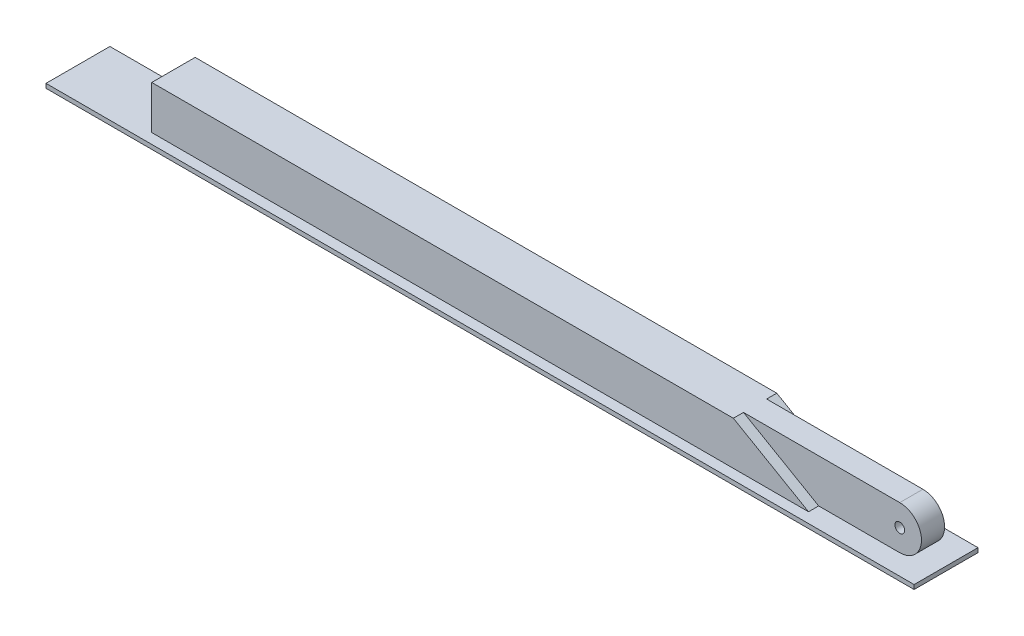
SolidWorks part; units mm, degrees
ref_plane "Front Plane" through (0, 0, 0) normal (0, 0, 1) x (1, 0, 0)
ref_plane "Top Plane" through (0, 0, 0) normal (0, 1, 0) x (1, 0, 0)
ref_plane "Right Plane" through (0, 0, 0) normal (1, 0, 0) x (0, 0, -1)
sketch "Sketch1" plane through (0, 0, 0) normal (0, 0, 1) x (1, 0, 0)
  line L0 (-225, 0) -> (225, 0) construction
  line L1 (-225, 15) -> (225, 15)
  line L2 (-225, -15) -> (225, -15)
  arc A0 (-225, 15) -> (-225, -15) centre (-225, 0) ccw
  arc A1 (225, -15) -> (225, 15) centre (225, 0) ccw
  point P2 (0, 0)
  dimension "D1" = 450
  dimension "D2" = 30
extrude "Boss-Extrude1" add sketch "Sketch1" along normal mid plane 30
hole_wizard "H (0.266) Diameter Hole1" positions "Sketch2" profile "Sketch4" hole size "H" standard "ANSI Inch" end condition through all
sketch "Sketch2" plane through (0, 0, 15) normal (0, 0, 1) x (1, 0, 0)
  point P0 (-225, 0)
  point P3 (225, 0)
sketch "Sketch4" plane through (-225, 0, 15) normal (1, 0, 0) x (0, -1, 0)
  line L0 (0, 0) -> (0, 30)
  line L1 (0, 30) -> (3.3782, 30)
  line L2 (3.3782, 30) -> (3.3782, 0)
  line L5 (3.3782, 0) -> (0, 0)
  line L11 (0, -6.35) -> (0, 107.95) construction
  dimension "Thru Hole Dia." = 6.7564
  dimension "Thru Hole Depth" = 30
sketch "Sketch5" plane through (0, 15, 0) normal (0, 1, 0) x (1, 0, 0)
  line L1 (-257, 8) -> (-217, 8)
  line L2 (-257, 8) -> (-257, -8)
  line L3 (-257, -8) -> (-217, -8)
  line L4 (-217, 8) -> (-217, -8)
  line L5 (-217, 0) -> (0, 0) construction
  line L6 (-225, -15) -> (-225, 15) construction
  line L7 (225, -15) -> (225, 15) construction
  line L8 (217, 28.9161) -> (257, 28.9161)
  line L9 (217, 28.9161) -> (217, 8)
  line L10 (217, 8) -> (257, 8)
  line L11 (257, 28.9161) -> (257, 8)
  line L12 (217, -28.9161) -> (257, -28.9161)
  line L13 (217, -28.9161) -> (217, -8)
  line L14 (217, -8) -> (257, -8)
  line L15 (257, -28.9161) -> (257, -8)
  dimension "D1" = 16
  dimension "D2" = 8
  dimension "D3" = 40
  dimension "D4" = 8
extrude "Cut-Extrude1" cut sketch "Sketch5" against normal through all
sketch "Sketch6" plane through (0, 15, 0) normal (0, 1, 0) x (1, 0, 0)
  line L0 (217, 15) -> (217, 8) construction
  line L1 (-262.0368, 59.0418) -> (167, 59.0418)
  line L2 (-262.0368, 59.0418) -> (-262.0368, -68.39)
  line L3 (-262.0368, -68.39) -> (167, -68.39)
  line L4 (167, 59.0418) -> (167, -68.39)
  dimension "D1" = 50
extrude "Cut-Extrude2" cut sketch "Sketch6" against normal through all
sketch "Sketch10" plane through (167, 0, 0) normal (-1, 0, 0) x (0, 0, 1)
  line L1 (15, -15) -> (-15, -15)
  line L2 (15, -15) -> (15, 15)
  line L3 (15, 15) -> (-15, 15)
  line L4 (-15, -15) -> (-15, 15)
  line L5 (15, -15) -> (-15, 15) construction
  line L6 (15, 15) -> (-15, -15) construction
  point P0 (0, 0)
extrude "Boss-Extrude3" add sketch "Sketch10" along normal blind 500
sketch "Sketch11" plane through (-333, 0, 0) normal (-1, 0, 0) x (0, 0, 1)
  circle A0 centre (0, 0) radius 9.525
  dimension "D1" = 19.05
extrude "Cut-Extrude4" cut sketch "Sketch11" against normal blind 400
sketch "Sketch13" plane through (0, -15, 0) normal (0, -1, 0) x (-1, 0, 0)
  line L0 (-250.0157, 22.0795) -> (-250.0157, -22.0795) construction
  line L1 (351, -22.0795) -> (-249, -22.0795)
  line L2 (351, -22.0795) -> (351, 22.0795)
  line L3 (351, 22.0795) -> (-249, 22.0795)
  line L4 (-249, -22.0795) -> (-249, 22.0795)
  line L5 (333, 15) -> (333, -15) construction
  line L8 (-249, 0) -> (0, 0) construction
  point P0 (0, 0)
  dimension "D1" = 600
  dimension "D2" = 18
extrude "Boss-Extrude4" add sketch "Sketch13" along normal blind 3
sketch "Sketch14" plane through (0, 15, 0) normal (0, 1, 0) x (1, 0, 0)
  line L0 (225, -8) -> (225, 8) construction
  line L1 (-396.0349, 53.7915) -> (-285, 53.7915)
  line L2 (-396.0349, 53.7915) -> (-396.0349, -58.394)
  line L3 (-396.0349, -58.394) -> (-285, -58.394)
  line L4 (-285, 53.7915) -> (-285, -58.394)
  dimension "D1" = 510
extrude "Cut-Extrude5" cut sketch "Sketch14" against normal up to surface (30 mm away) up to face at (-51, -15, 0)
chamfer "Chamfer1" distance 100 angle 30 2 edges at (217, 15, -11.5) (217, 15, 11.5) first distance on face at (93.5, 15, 0)
